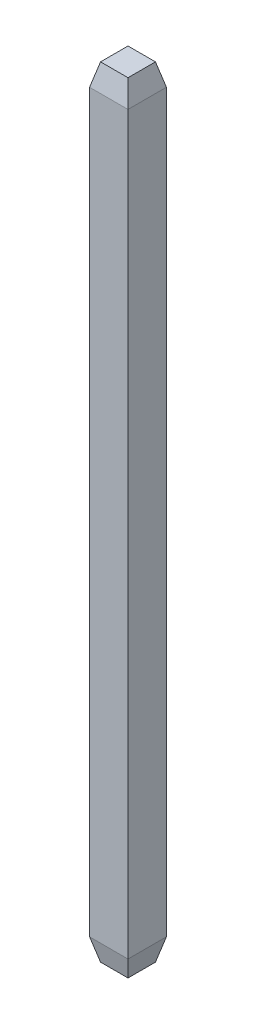
SolidWorks part; units mm, degrees
ref_plane "Спереди" through (0, 0, 0) normal (0, 0, 1) x (1, 0, 0)
ref_plane "Сверху" through (0, 0, 0) normal (0, 1, 0) x (1, 0, 0)
ref_plane "Справа" through (0, 0, 0) normal (1, 0, 0) x (0, 0, -1)
sketch "Эскиз1" plane through (0, 0, 0) normal (0, 1, 0) x (1, 0, 0)
  line L1 (-0.35, -0.35) -> (0.35, -0.35)
  line L2 (-0.35, -0.35) -> (-0.35, 0.35)
  line L3 (-0.35, 0.35) -> (0.35, 0.35)
  line L4 (0.35, -0.35) -> (0.35, 0.35)
  dimension "D1" = 0.7
  dimension "D2" = 0.7
  dimension "D3" = 0.35
  dimension "D4" = 0.35
extrude "Бобышка-Вытянуть1" add sketch "Эскиз1" along normal blind 14.2
chamfer "Фаска1" distance 0.4 distance2 0.1 4 edges at (0, 14.2, -0.35) (-0.35, 14.2, 0) (0, 14.2, 0.35) (0.35, 14.2, 0) first distance on face at (0, 7.1, -0.35) first distance on face at (-0.35, 7.1, 0) first distance on face at (0, 7.1, 0.35) first distance on face at (0.35, 7.1, 0)
chamfer "Фаска2" distance 0.1 distance2 0.4 4 edges at (0, 0, 0.35) (-0.35, 0, 0) (0, 0, -0.35) (0.35, 0, 0) first distance on face at (0, 0, 0)
ref_axis "Ось1" through (0, 0, 0) along (0, 1, 0)
